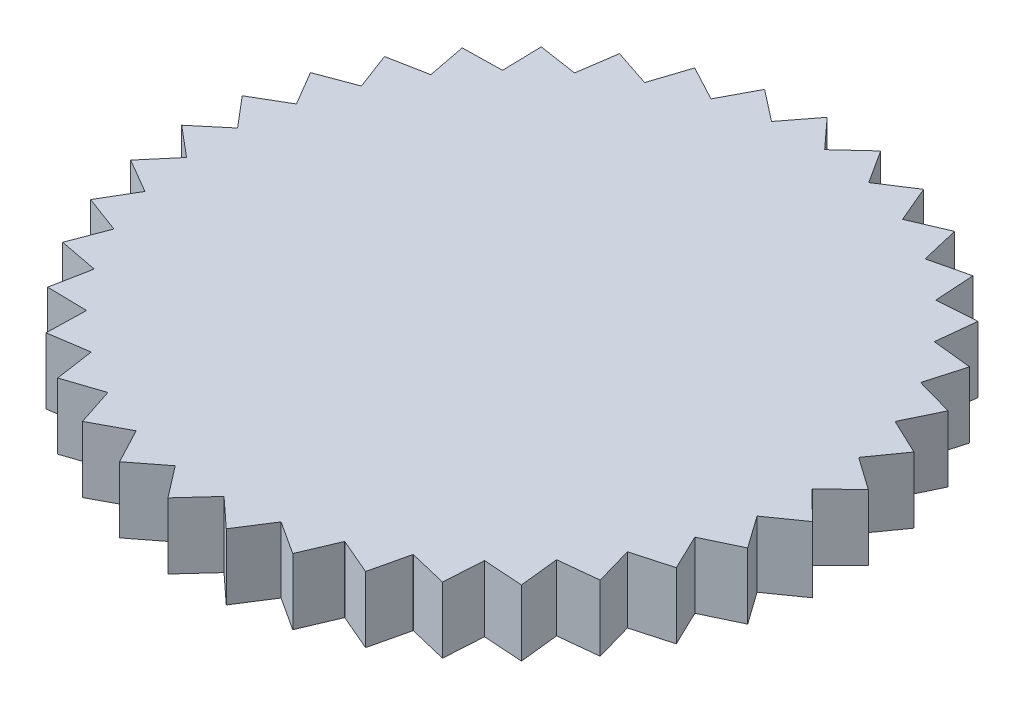
SolidWorks part; units mm, degrees
ref_plane "Front Plane" through (0, 0, 0) normal (0, 0, 1) x (1, 0, 0)
ref_plane "Top Plane" through (0, 0, 0) normal (0, 1, 0) x (1, 0, 0)
ref_plane "Right Plane" through (0, 0, 0) normal (1, 0, 0) x (0, 0, -1)
sketch "Sketch1" plane through (0, 0, 0) normal (0, 1, 0) x (1, 0, 0)
  line L0 (0, 0) -> (-10, 0) construction
  line L1 (-10, 0) -> (-9.0812, 0.771)
  line L3 (-9.0812, -0.771) -> (-10, 0)
  line L4 (-9.8562, 1.69) -> (-8.8202, 2.2946)
  line L5 (-9.0808, 0.7748) -> (-9.8562, 1.69)
  line L6 (-9.4288, 3.3314) -> (-8.3056, 3.7523)
  line L7 (-8.8193, 2.2983) -> (-9.4288, 3.3314)
  line L8 (-8.7301, 4.8769) -> (-7.552, 5.1019)
  line L9 (-8.304, 3.7557) -> (-8.7301, 4.8769)
  line L10 (-7.7804, 6.2822) -> (-6.5811, 6.3048)
  line L11 (-7.5498, 5.1051) -> (-7.7804, 6.2822)
  line L12 (-6.6067, 7.5067) -> (-5.4209, 7.3264)
  line L13 (-6.5785, 6.3076) -> (-6.6067, 7.5067)
  line L14 (-5.2431, 8.5153) -> (-4.1048, 8.1371)
  line L15 (-5.4178, 7.3286) -> (-5.2431, 8.5153)
  line L16 (-3.7286, 9.2789) -> (-2.6706, 8.7138)
  line L17 (-4.1014, 8.1388) -> (-3.7286, 9.2789)
  line L18 (-2.1068, 9.7756) -> (-1.1595, 9.0398)
  line L19 (-2.6669, 8.7149) -> (-2.1068, 9.7756)
  line L20 (-0.4244, 9.991) -> (0.3849, 9.1057)
  line L21 (-1.1557, 9.0403) -> (-0.4244, 9.991)
  line L22 (1.2702, 9.919) -> (1.9182, 8.9097)
  line L23 (0.3887, 9.1055) -> (1.2702, 9.919)
  line L24 (2.9282, 9.5617) -> (3.3964, 8.4573)
  line L25 (1.922, 8.9089) -> (2.9282, 9.5617)
  line L26 (4.502, 8.9293) -> (4.7768, 7.7617)
  line L27 (3.3999, 8.4559) -> (4.502, 8.9293)
  line L28 (5.9463, 8.04) -> (6.0198, 6.8428)
  line L29 (4.7801, 7.7597) -> (5.9463, 8.04)
  line L30 (7.2196, 6.9194) -> (7.0897, 5.727)
  line L31 (6.0227, 6.8402) -> (7.2196, 6.9194)
  line L32 (8.2851, 5.5997) -> (7.9556, 4.4464)
  line L33 (7.0921, 5.724) -> (8.2851, 5.5997)
  line L34 (9.1123, 4.119) -> (8.5926, 3.038)
  line L35 (7.9574, 4.4431) -> (9.1123, 4.119)
  line L36 (9.6773, 2.5198) -> (8.9824, 1.5421)
  line L37 (8.5939, 3.0344) -> (9.6773, 2.5198)
  line L38 (9.964, 0.8481) -> (9.1138, 0.0019)
  line L39 (8.9831, 1.5384) -> (9.964, 0.8481)
  line L40 (9.964, -0.8481) -> (8.9831, -1.5384)
  line L41 (9.1138, -0.0019) -> (9.964, -0.8481)
  line L42 (9.6773, -2.5198) -> (8.5939, -3.0344)
  line L43 (8.9824, -1.5421) -> (9.6773, -2.5198)
  line L44 (9.1123, -4.119) -> (7.9574, -4.4431)
  line L45 (8.5926, -3.038) -> (9.1123, -4.119)
  line L46 (8.2851, -5.5997) -> (7.0921, -5.724)
  line L47 (7.9556, -4.4464) -> (8.2851, -5.5997)
  line L48 (7.2196, -6.9194) -> (6.0227, -6.8402)
  line L49 (7.0897, -5.727) -> (7.2196, -6.9194)
  line L50 (5.9463, -8.04) -> (4.7801, -7.7597)
  line L51 (6.0198, -6.8428) -> (5.9463, -8.04)
  line L52 (4.502, -8.9293) -> (3.3999, -8.4559)
  line L53 (4.7768, -7.7617) -> (4.502, -8.9293)
  line L54 (2.9282, -9.5617) -> (1.922, -8.9089)
  line L55 (3.3964, -8.4573) -> (2.9282, -9.5617)
  line L56 (1.2702, -9.919) -> (0.3887, -9.1055)
  line L57 (1.9182, -8.9097) -> (1.2702, -9.919)
  line L58 (-0.4244, -9.991) -> (-1.1557, -9.0403)
  line L59 (0.3849, -9.1057) -> (-0.4244, -9.991)
  line L60 (-2.1068, -9.7756) -> (-2.6669, -8.7149)
  line L61 (-1.1595, -9.0398) -> (-2.1068, -9.7756)
  line L62 (-3.7286, -9.2789) -> (-4.1014, -8.1388)
  line L63 (-2.6706, -8.7138) -> (-3.7286, -9.2789)
  line L64 (-5.2431, -8.5153) -> (-5.4178, -7.3286)
  line L65 (-4.1048, -8.1371) -> (-5.2431, -8.5153)
  line L66 (-6.6067, -7.5067) -> (-6.5785, -6.3076)
  line L67 (-5.4209, -7.3264) -> (-6.6067, -7.5067)
  line L68 (-7.7804, -6.2822) -> (-7.5498, -5.1051)
  line L69 (-6.5811, -6.3048) -> (-7.7804, -6.2822)
  line L70 (-8.7301, -4.8769) -> (-8.304, -3.7557)
  line L71 (-7.552, -5.1019) -> (-8.7301, -4.8769)
  line L72 (-9.4288, -3.3314) -> (-8.8193, -2.2983)
  line L73 (-8.3056, -3.7523) -> (-9.4288, -3.3314)
  line L74 (-9.8562, -1.69) -> (-9.0808, -0.7748)
  line L75 (-8.8202, -2.2946) -> (-9.8562, -1.69)
  circle A0 centre (0, 0) radius 10 construction
  circle A1 centre (0, 0) radius 9.1138
  point P3 (0, 0)
  point P117 (0, 0)
  dimension "D1" = 10
  dimension "D2" = 40
  dimension "D3" = 40
  dimension "D4" = 37
extrude "Boss-Extrude2" add sketch "Sketch1" along normal blind 2 contours A1 L58 L59 | A1 L56 L57 | A1 L54 L55 | A1 L52 L53 | A1 L50 L51 | A1 L48 L49 | A1 L46 L47 | A1 L44 L45 | A1 L42 L43 | A1 L40 L41 | A1 L38 L39 | A1 L36 L37 | A1 L34 L35 | A1 L32 L33 | A1 L30 L31 | A1 L28 L29 | A1 L26 L27 | A1 L24 L25 | A1 L22 L23 | A1 L20 L21 | A1 L18 L19 | A1 L16 L17 | A1 L14 L15 | A1 L12 L13 | A1 L10 L11 | A1 L8 L9 | A1 L6 L7 | A1 L4 L5 | A1 L1 L3 | A1 L74 L75 | A1 L72 L73 | A1 L70 L71 | A1 L68 L69 | A1 L66 L67 | A1 L64 L65 | A1 L62 L63 | A1 L60 L61 region at (-9.402, 0, 0) region at (-9.2668, 0, -1.589) region at (-9.2668, 0, 1.589) region at (-8.865, 0, -3.1322) region at (-8.865, 0, 3.1322) region at (-8.2081, 0, -4.5853) region at (-8.2081, 0, 4.5853) region at (-7.3151, 0, -5.9065) region at (-7.3151, 0, 5.9065) region at (-6.2117, 0, -7.0578) region at (-6.2117, 0, 7.0578) region at (-4.9296, 0, -8.0061) region at (-4.9296, 0, 8.0061) region at (-3.5056, 0, -8.724) region at (-3.5056, 0, 8.724) region at (-1.9808, 0, -9.191) region at (-1.9808, 0, 9.191) region at (-0.399, 0, -9.3936) region at (-0.399, 0, 9.3936) region at (1.1942, 0, -9.3259) region at (1.1942, 0, 9.3259) region at (2.7531, 0, -8.9899) region at (2.7531, 0, 8.9899) region at (4.2328, 0, -8.3953) region at (4.2328, 0, 8.3953) region at (5.5908, 0, -7.5592) region at (5.5908, 0, 7.5592) region at (6.7879, 0, -6.5056) region at (6.7879, 0, 6.5056) region at (7.7897, 0, -5.2649) region at (7.7897, 0, 5.2649) region at (8.5674, 0, -3.8727) region at (8.5674, 0, 3.8727) region at (9.0987, 0, -2.3691) region at (9.0987, 0, 2.3691) region at (9.3682, 0, -0.7973) region at (9.3682, 0, 0.7973)
extrude "Boss-Extrude3" add sketch "Sketch1<7>" along normal blind 2 contours A1 region at (0, 0, 0)
sketch "Sketch1<7>" plane through (0, 0, 0) normal (0, 1, 0) x (1, 0, 0) same geometry as "Sketch1"
